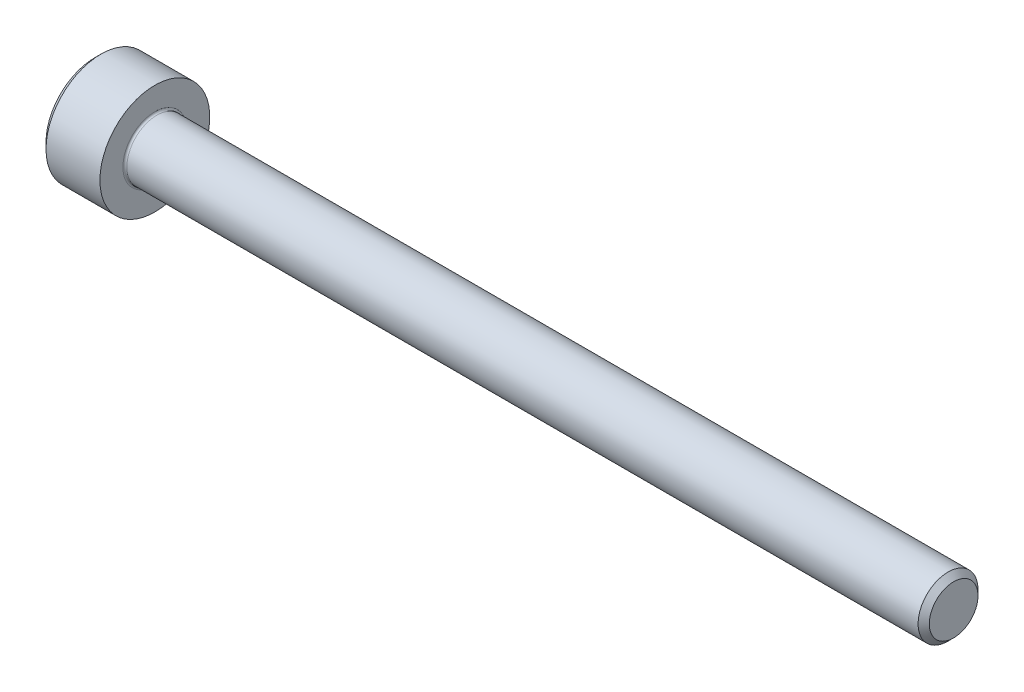
SolidWorks part; units mm, degrees
note: '?' marks a value the reader was unsure of.
revolve "Base-Revolve" add sketch "BodySke"
sketch "BodySke" plane through (0, 0, 0) normal (0, 0, 1) x (1, 0, 0)
  line L0 (0, 0) -> (0, 2.45)
  line L1 (0.3, 2.75) -> (3, 2.75)
  line L2 (3, 2.75) -> (3, 1.5)
  line L3 (3, 1.5) -> (42.7195, 1.5)
  line L4 (43, 1.2195) -> (43, 0)
  line L5 (43, 0) -> (0, 0)
  line L6 (-31.75, 0) -> (127, 0) construction
  line L7 (0, 2.45) -> (0.3, 2.75)
  line L8 (43, 1.2195) -> (42.7195, 1.5)
  line L9 (0, -2.45) -> (0.3, -2.75) construction
  line L10 (43, -1.2195) -> (42.7195, -1.5) construction
  line L11 (3.5, 9.525) -> (3.5, 3.175) construction
  line L12 (38, 9.525) -> (38, 3.175) construction
  line L13 (-7, 9.525) -> (-7, 3.175) construction
  dimension "Diameter" = 3
  dimension "Head_ht" = 3
  dimension "Length" = 40
  dimension "Body_ch_ang" = 45
  dimension "Head_dia" = 5.5
  dimension "Head_ch_ang" = 45
  dimension "Minor_dia" = 2.439
  dimension "Advance" = 0.5
  dimension "Thread_nom" = 5
  dimension "Thread_length" = 50
  dimension "Head_ch_ht" = 0.3
cosmetic thread "ThreadCosmetic" [suppressed]
fillet "Fillet1" radius 0.1 1 edges at (3, 0, 1.5)
ref_plane "Plane1" through (0, 0, 0) normal (0, 0, 1) x (1, 0, 0)
ref_plane "Plane2" through (0, 0, 0) normal (0, 1, 0) x (1, 0, 0)
ref_plane "Plane3" through (0, 0, 0) normal (1, 0, 0) x (0, 0, -1)
sketch "Sketch2" plane through (0, 0, 0) normal (0, 0, 1) x (1, 0, 0)
  line L0 (0, 1.28) -> (1.3, 1.28)
  line L1 (1.3, 1.28) -> (2.039, 0)
  line L2 (-31.75, 0) -> (127, 0) construction
  line L3 (2.039, 0) -> (0, 0)
  line L4 (0, 0) -> (0, 1.28)
  line L5 (0, 2.45) -> (0, -2.45) construction
  line L6 (0, 0) -> (47.625, 0) construction
  line L7 (3, -2.75) -> (3, 2.75) construction
  dimension "D1" = 1.28
  dimension "D2" = 60
revolve "Hex-PreBroach" cut sketch "Sketch2" angle 360 about L6
sketch "Sketch3" plane through (0, 0, 0) normal (-1, 0, 0) x (0, 0.5, 0.866)
  line L0 (0.739, 1.28) -> (-0.739, 1.28)
  line L1 (-0.739, 1.28) -> (-1.478, 0)
  line L2 (0.739, 1.28) -> (1.478, 0)
  line L3 (0.739, -1.28) -> (1.478, 0)
  line L4 (0.739, -1.28) -> (-0.739, -1.28)
  line L5 (-0.739, -1.28) -> (-1.478, 0)
  dimension "D1" = 1.28
  dimension "D2" = 1.28
extrude "Hex" cut sketch "Sketch3" against normal blind 1.3
sketch "Sketch4" plane through (0, 0, 0) normal (-1, 0, 0) x (0, 0, 1)
  line L0 (0, 0) -> (1.4605, 0)
  line L1 (0, 0) -> (6.1484, 3.5498) construction
  line L2 (0, 0) -> (0.7302, 1.2648)
  line L3 (1.2009, 0.3267) -> (1.3933, 0.4378)
  line L4 (0.8834, 0.8767) -> (1.0758, 0.9877)
  arc A0 (1.2009, 0.3267) -> (0.8834, 0.8767) centre (0, 0) ccw
  arc A1 (1.4605, 0) -> (1.3933, 0.4378) centre (0, 0) ccw
  arc A2 (0.7302, 1.2648) -> (1.0758, 0.9877) centre (0, 0) cw
  dimension "D1" = 30
  dimension "D2" = 60
  dimension "Spline_p_dim" = 0.635
  dimension "D3" = 0.3175
extrude "Spline" [suppressed] cut sketch "Sketch4" against normal blind 1.3
pattern_circular "CirPattern1" [suppressed] count 0 every? 60?
sketch "Sketch5" plane through (0, 0, 0) normal (0, 0, 1) x (1, 0, 0)
  line L0 (-31.75, 0) -> (127, 0) construction
  line L2 (0, 2.45) -> (0, -2.45) construction
  circle A0 centre (1.2, 0) radius 0.475
  dimension "Drilled_hole_dia" = 0.95
  dimension "Drilled_hole_loc" = 1.2
extrude "Hole" [suppressed] cut sketch "Sketch5" against normal through all and the other way through all
pattern_circular "Drilled-4" [suppressed] count 2 every 60
pattern_circular "Drilled-6" [suppressed] count 3 every 60
sketch "ThdSchSke" plane through (0, 0, 0) normal (0, 0, 1) x (1, 0, 0)
  line L0 (3.5, -1.2195) -> (3.3036, -1.5)
  line L1 (3.5, -1.2195) -> (3.6964, -1.5)
  line L2 (3.6964, -1.5) -> (3.6964, -1.875)
  line L3 (-3.175, 0) -> (5.1513, 0) construction
  line L5 (3.6964, -1.875) -> (3.3036, -1.875)
  line L6 (3.3036, -1.875) -> (3.3036, -1.5)
  line L7 (0, 2.45) -> (0, -2.45) construction
  dimension "Thread_minor" = 2.439
  dimension "Diameter" = 3
revolve "ThreadSchematic" [suppressed] cut sketch "ThdSchSke" angle 360 about L3
pattern_linear "ThdSchPat" [suppressed]
equation "\"D2@Sketch3\" = \"Hex_size@Sketch3\" / 2"
equation "\"D1@Sketch3\" = \"Hex_size@Sketch3\" / 2"
equation "\"D1@Sketch2\" = \"Hex_size@Sketch3\" / 2"
equation "\"D3@Sketch4\" = \"Spline_p_dim@Sketch4\" / 2"
equation "\"Thread_minor@ThreadCosmetic\"  =  \"Minor_dia@BodySke\""
equation "\"D2@CirPattern1\" = 360 / \"Num_teeth@CirPattern1\""
equation "\"Wall_thickness@Sketch2\" = \"Head_ht@BodySke\" - \"Key_eng@Hex\""
equation "\"Thread_length@ThreadCosmetic\" = ((sgn( (\"Length@BodySke\" - \"Advance@BodySke\" ) - \"Thread_nom@BodySke\" )-1)*( (\"Length@BodySke\" - \"Advance@BodySke\" ) - \"Thread_nom@BodySke\" ))/-2+ \"Thread_nom@BodySke\""
equation "\"Thread_minor@ThdSchSke\" = \"Minor_dia@BodySke\""
equation "\"Diameter@ThdSchSke\" = \"Diameter@BodySke\""
equation "\"Overcut@ThdSchSke\" = \"Diameter@BodySke\" * 1.25"
equation "\"Start@ThdSchSke\" = \"Head_ht@BodySke\" + \"Length@BodySke\" - \"Thread_length@ThreadCosmetic\"  '---Non-countersunk---"
equation "\"Num_threads@ThdSchPat\" = int( \"Thread_length@ThreadCosmetic\" / \"Advance@BodySke\" + 0.999 )  + 1"
equation "\"Advance@ThdSchPat\" = \"Thread_length@ThreadCosmetic\" /  (\"Num_threads@ThdSchPat\" - 1) 'relax it"
equation "\"Num_threads@ThdSchPat\" = \"Num_threads@ThdSchPat\" - sgn( \"Num_threads@ThdSchPat\" - 1) '---chamfered tips only---"
